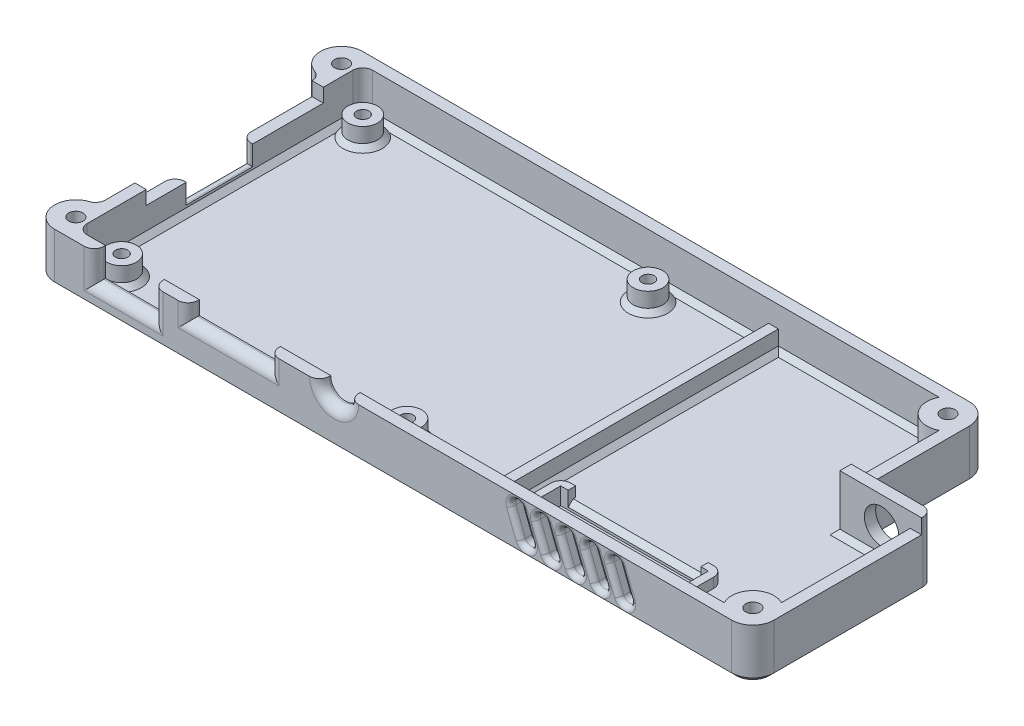
SolidWorks part; units mm, degrees
ref_plane "Front Plane" through (0, 0, 0) normal (0, 0, 1) x (1, 0, 0)
ref_plane "Top Plane" through (0, 0, 0) normal (0, 1, 0) x (1, 0, 0)
ref_plane "Right Plane" through (0, 0, 0) normal (1, 0, 0) x (0, 0, -1)
sketch "Sketch1" plane through (0, 0, 0) normal (0, 1, 0) x (1, 0, 0)
  line L0 (-71.5618, 3.106) -> (49.4382, 3.106) construction
  line L1 (-71.5618, 31.106) -> (49.4382, 31.106)
  line L2 (-71.5618, 31.106) -> (-71.5618, -24.894)
  line L3 (-71.5618, -24.894) -> (49.4382, -24.894)
  line L4 (49.4382, 31.106) -> (49.4382, -24.894)
  line L5 (-60.6618, -24.894) -> (-60.6618, -31.6828) construction
  line L6 (-68.0618, 27.606) -> (-10.0618, 27.606)
  line L7 (-68.0618, 27.606) -> (-68.0618, -21.394)
  line L8 (-68.0618, -21.394) -> (-10.0618, -21.394)
  line L9 (-10.0618, 27.606) -> (-10.0618, -21.394)
  line L10 (-39.5618, -24.894) -> (-39.5618, -31.6828) construction
  line L11 (-18.0618, -24.894) -> (-18.0618, -31.6828) construction
  line L12 (-65.4118, -26.5648) -> (-55.9118, -26.5648) construction
  line L13 (-48.0618, -26.5648) -> (-31.0618, -26.5648) construction
  line L14 (-22.0618, -26.5648) -> (-14.0618, -26.5648) construction
  line L15 (-72.5618, 9.606) -> (-72.5618, -3.394) construction
  line L16 (-71.5618, 3.106) -> (-72.5618, 3.106) construction
  dimension "D1" = 121
  dimension "D2" = 56
  dimension "D3" = 49
  dimension "D4" = 58
  dimension "D5" = 3.5
  dimension "D6" = 3.5
  dimension "D7" = 10.9
  dimension "D8" = 32
  dimension "D9" = 53.5
  dimension "D10" = 2
  dimension "D11" = 13
  dimension "D12" = 9.5
  dimension "D13" = 17
  dimension "D14" = 8
sketch "Sketch3" plane through (0, 0, 0) normal (0, 1, 0) x (1, 0, 0)
  line L0 (55.0382, -25.894) -> (64.7382, -25.894)
  line L1 (52.7382, 8.406) -> (67.0382, 8.406)
  line L2 (55.0382, 6.106) -> (64.7382, 6.106) construction
  line L3 (52.7382, -28.194) -> (67.0382, -28.194)
  line L4 (52.7382, 34.406) -> (-74.8618, 34.406)
  line L5 (-74.8618, 34.406) -> (-74.8618, -28.194)
  line L6 (-74.8618, -28.194) -> (52.7382, -28.194)
  line L7 (52.7382, 8.406) -> (52.7382, 34.406)
  line L8 (50.4382, 32.106) -> (-72.5618, 32.106)
  line L9 (50.4382, -25.894) -> (50.4382, 32.106)
  line L10 (-72.5618, -25.894) -> (50.4382, -25.894)
  line L11 (-72.5618, 32.106) -> (-72.5618, -25.894)
  line L12 (50.4382, 32.106) -> (-72.5618, 32.106)
  line L13 (50.4382, 6.106) -> (50.4382, 32.106)
  line L14 (-72.5618, -25.894) -> (50.4382, -25.894)
  line L15 (-72.5618, 32.106) -> (-72.5618, -25.894)
  line L16 (-11.0618, 3.106) -> (-11.0618, 34.406) construction
  line L17 (-71.5618, 3.106) -> (49.4382, 3.106) construction
  line L18 (67.0382, 8.406) -> (67.0382, -28.194)
  line L19 (64.7382, 6.106) -> (64.7382, -25.894)
  line L20 (-74.8618, 3.106) -> (52.7382, 3.106) construction
  line L21 (50.4382, 6.106) -> (64.7382, 6.106)
  line L22 (55.0382, -25.894) -> (50.4382, -25.894)
  line L23 (55.0382, 6.106) -> (55.0382, -25.894) construction
  line L24 (52.7382, 8.406) -> (52.7382, -28.194) construction
  line L25 (52.7382, -28.194) -> (52.7382, 34.406) construction
  line L26 (50.4382, -25.894) -> (50.4382, 32.106) construction
  dimension "D3" = 2.3
  dimension "D4" = 26
  dimension "D5" = 12
  dimension "D1" = 1
  dimension "D2" = 2.3
extrude "Boss-Extrude1" add sketch "Sketch3" along normal blind 10.3
sketch "Sketch5" plane through (0, 0, 0) normal (0, 1, 0) x (1, 0, 0)
  line L1 (-72.5618, 32.106) -> (50.4382, 32.106)
  line L2 (-72.5618, 32.106) -> (-72.5618, -25.894)
  line L3 (-72.5618, -25.894) -> (50.4382, -25.894)
  line L4 (50.4382, 32.106) -> (50.4382, 6.106)
  line L5 (50.4382, 6.106) -> (64.7382, 6.106)
  line L7 (50.4382, -25.894) -> (64.7382, -25.894)
  line L8 (64.7382, 6.106) -> (64.7382, -25.894)
extrude "Boss-Extrude2" add sketch "Sketch5" along normal blind 2
sketch "Sketch6" plane through (0, 2, 0) normal (0, 1, 0) x (1, 0, 0)
  circle A0 centre (-68.0618, 27.606) radius 3
  circle A1 centre (-68.0618, -21.394) radius 3
  circle A2 centre (-10.0618, -21.394) radius 3
  circle A3 centre (-10.0618, 27.606) radius 3
extrude "Boss-Extrude3" add sketch "Sketch6" along normal blind 4
hole_wizard "Ø2.5 (2.5) Diameter Hole1" positions "Sketch8" profile "Sketch9" hole size "Ø2.5" standard "ANSI Metric"
sketch "Sketch8" plane through (0, 6, 0) normal (0, 1, 0) x (1, 0, 0)
  point P0 (-68.0618, 27.606)
  point P3 (-10.0618, 27.606)
  point P6 (-10.0618, -21.394)
  point P9 (-68.0618, -21.394)
sketch "Sketch9" plane through (-68.0618, 6, -27.606) normal (1, 0, 0) x (0, 0, 1)
  line L0 (0, 0) -> (0, 8.7511)
  line L1 (0, 8.7511) -> (1.25, 8)
  line L2 (1.25, 8) -> (1.25, 0)
  line L5 (1.25, 0) -> (0, 0)
  line L10 (0, 8.7511) -> (-1.25, 8) construction
  line L11 (0, -6.35) -> (0, 107.95) construction
  dimension "Hole Dia." = 2.5
  dimension "Hole Depth" = 8
  dimension "Drill Angle" = 118
sketch "Sketch10" plane through (0, 2, 0) normal (0, 1, 0) x (1, 0, 0)
  line L0 (50.4382, 32.106) -> (-72.5618, 32.106) construction
  line L1 (9.9382, 32.106) -> (11.9382, 32.106)
  line L2 (9.9382, 32.106) -> (9.9382, -25.894)
  line L3 (9.9382, -25.894) -> (11.9382, -25.894)
  line L4 (11.9382, 32.106) -> (11.9382, -25.894)
  line L5 (-72.5618, -25.894) -> (64.7382, -25.894) construction
  line L6 (-10.0618, 27.606) -> (-10.0618, -21.394) construction
  dimension "D1" = 2
  dimension "D2" = 20
extrude "Boss-Extrude4" add sketch "Sketch10" along normal blind 4
sketch "Sketch11" plane through (0, 0, 28.194) normal (0, 0, 1) x (1, 0, 0)
  line L0 (-74.8618, 10.3) -> (-74.8618, 0) construction
  line L1 (-66.8618, 10.3) -> (-54.8618, 10.3)
  line L2 (-66.8618, 10.3) -> (-66.8618, 4.5)
  line L3 (-66.8618, 4.5) -> (-54.8618, 4.5)
  line L4 (-54.8618, 10.3) -> (-54.8618, 4.5)
  line L5 (-74.8618, 0) -> (67.0382, 0) construction
  line L6 (-60.8618, 10.3) -> (-60.6618, 0) construction
  line L7 (-65.4118, 0) -> (-55.9118, 0) construction
  line L9 (-47.778, 10.3) -> (-31.278, 10.3)
  line L10 (-47.778, 10.3) -> (-47.778, 7.5)
  line L11 (-47.778, 7.5) -> (-31.278, 7.5)
  line L12 (-31.278, 10.3) -> (-31.278, 7.5)
  line L13 (-68.0618, 0) -> (-10.0618, 0) construction
  line L14 (-39.5618, 0) -> (-39.528, 10.3) construction
  line L15 (-48.0618, 0) -> (-31.0618, 0) construction
  line L16 (-18.0618, 0) -> (-18.0618, 10.3) construction
  line L17 (-22.0618, 0) -> (-14.0618, 0) construction
  line L18 (-74.8618, 10.3) -> (67.0382, 10.3) construction
  circle A0 centre (-18.0618, 10.3) radius 3
  dimension "D5" = 6
  dimension "D1" = 4.5
  dimension "D2" = 12
  dimension "D3" = 7.5
  dimension "D4" = 16.5
  dimension "D6" = 8
extrude "Cut-Extrude1" cut sketch "Sketch11" against normal up to next
sketch "Sketch12" plane through (-74.8618, 0, 0) normal (-1, 0, 0) x (0, 0, 1)
  line L0 (-3.106, 0) -> (-3.106, 10.3) construction
  line L1 (-27.606, 0) -> (21.394, 0) construction
  line L2 (-34.406, 10.3) -> (28.194, 10.3) construction
  line L4 (-9.7329, 10.3) -> (3.7671, 10.3)
  line L5 (-9.7329, 10.3) -> (-9.7329, 3.5)
  line L6 (-9.7329, 3.5) -> (3.7671, 3.5)
  line L7 (3.7671, 10.3) -> (3.7671, 3.5)
  line L8 (-24.106, 10.3) -> (11.894, 10.3)
  line L9 (-24.106, 10.3) -> (-24.106, 7.5)
  line L10 (-24.106, 7.5) -> (11.894, 7.5)
  line L11 (11.894, 10.3) -> (11.894, 7.5)
  dimension "D1" = 13.5
  dimension "D2" = 3.5
  dimension "D3" = 7.5
  dimension "D4" = 36
extrude "Cut-Extrude2" cut sketch "Sketch12" against normal up to next contours L10 L11 L8 L9 | L7 L6 L5 L4
fillet "Fillet6" radius 2 1 edges at (50.4382, 6.15, -32.106)
fillet "Fillet8" radius 2 2 edges at (-72.5618, 6.15, 25.894) (-72.5618, 6.15, -32.106)
chamfer "Chamfer1" distance 1 angle 45 4 edges at (-68.0618, 2, 24.394) (-10.0618, 2, 24.394) (-10.0618, 2, -24.606) (-68.0618, 2, -24.606)
chamfer "Chamfer2" distance 1 angle 45 13 edges at (11.9382, 2, -3.106) (38.3382, 2, 25.894) (30.1882, 2, -32.106) (49.8524, 2, -31.5202) (50.4382, 2, -18.106) (-30.3118, 2, 25.894) (-71.976, 2, 25.3082) (-72.5618, 2, -3.106) (-71.976, 2, -31.5202) (9.9382, 2, -3.106) (-30.3118, 2, -32.106) (64.7382, 2, 9.894) (57.5882, 2, -6.106)
fillet "Fillet9" radius 2 9 edges at (-74.8618, 5.5, -9.7329) (-74.8618, 3.5, -2.9829) (-74.8618, 5.5, 3.7671) (-18.0618, 7.3, 28.194) (-31.278, 8.9, 28.194) (-47.778, 8.9, 28.194) (-39.528, 7.5, 28.194) (-54.8618, 7.4, 28.194) (-60.8618, 4.5, 28.194)
sketch "Sketch14" plane through (0, 10.3, 0) normal (0, 1, 0) x (1, 0, 0)
  line L1 (50.4382, 6.106) -> (67.0382, 6.106)
  line L2 (50.4382, 6.106) -> (50.4382, 8.406)
  line L3 (50.4382, 8.406) -> (67.0382, 8.406)
  line L4 (67.0382, 6.106) -> (67.0382, 8.406)
extrude "Boss-Extrude5" add sketch "Sketch14" along normal blind 3
sketch "Sketch13" plane through (0, 0, -8.406) normal (0, 0, -1) x (-1, 0, 0)
  circle A0 centre (-58.909, 7.7223) radius 3.5
extrude "Cut-Extrude3" cut sketch "Sketch13" against normal up to next
sketch "Sketch17" plane through (0, 0, 0) normal (0, 1, 0) x (1, 0, 0)
  line L0 (-74.8618, 34.406) -> (-74.8618, 24.106) construction
  line L1 (-74.8618, 34.406) -> (-74.8618, 25.806)
  line L2 (-74.8618, 25.806) -> (-74.659, 25.9406)
  line L3 (-74.8618, -19.594) -> (-74.8618, -28.194)
  line L4 (-74.8618, -28.194) -> (-74.659, -28.0594)
  arc A0 (-74.8618, -19.594) -> (-74.8618, -28.194) centre (-74.8618, -23.894) ccw
  arc A1 (-74.8618, 34.406) -> (-74.8618, 25.806) centre (-74.8618, 30.106) ccw
extrude "Boss-Extrude6" add sketch "Sketch17" along normal up to vertex (10.3 mm away) contours L1 A1 | L3 A0 region at (-76.6867, 0, -30.106) region at (-76.6867, 0, 23.894) up to point (-74.8618, 10.3, 28.194)
hole_wizard "Ø2.9 (2.9) Diameter Hole2" positions "Sketch19" profile "Sketch18" hole size "Ø2.9" standard "ANSI Metric" end condition up to next
sketch "Sketch19" plane through (0, 10.3, 0) normal (0, 1, 0) x (1, 0, 0)
  point P0 (-74.8618, 30.106)
sketch "Sketch18" plane through (-74.8618, 10.3, -30.106) normal (1, 0, 0) x (0, 0, 1)
  line L0 (0, 0) -> (0, 10.3)
  line L1 (0, 10.3) -> (1.45, 10.3)
  line L2 (1.45, 10.3) -> (1.45, 0)
  line L5 (1.45, 0) -> (0, 0)
  line L11 (0, -6.35) -> (0, 107.95) construction
  dimension "Thru Hole Dia." = 2.9
  dimension "Thru Hole Depth" = 10.3
hole_wizard "Ø2.9 (2.9) Diameter Hole1" positions "Sketch21" profile "Sketch20" hole size "Ø2.9" standard "ANSI Metric" end condition up to next
sketch "Sketch21" plane through (0, 10.3, 0) normal (0, 1, 0) x (1, 0, 0)
  point P0 (-74.8618, -23.894)
sketch "Sketch20" plane through (-74.8618, 10.3, 23.894) normal (1, 0, 0) x (0, 0, 1)
  line L0 (0, 0) -> (0, 10.3)
  line L1 (0, 10.3) -> (1.45, 10.3)
  line L2 (1.45, 10.3) -> (1.45, 0)
  line L5 (1.45, 0) -> (0, 0)
  line L11 (0, -6.35) -> (0, 107.95) construction
  dimension "Thru Hole Dia." = 2.9
  dimension "Thru Hole Depth" = 10.3
sketch "Sketch24" plane through (0, 2, 0) normal (0, 1, 0) x (1, 0, 0)
  circle A0 centre (62.7384, -23.8858) radius 4.3
  circle A1 centre (48.4185, 30.106) radius 4.3
extrude "Boss-Extrude7" add sketch "Sketch24" along normal up to surface (8.3 mm away) up to face at (-74.8618, 10.3, 25.344)
hole_wizard "Ø2.9 (2.9) Diameter Hole3" positions "Sketch26" profile "Sketch25" hole size "Ø2.9" standard "ANSI Metric" end condition up to next
sketch "Sketch26" plane through (0, 10.3, 0) normal (0, 1, 0) x (1, 0, 0)
  point P0 (62.7384, -23.8858)
sketch "Sketch25" plane through (62.7384, 10.3, 23.8858) normal (1, 0, 0) x (0, 0, 1)
  line L0 (0, 0) -> (0, 10.3)
  line L1 (0, 10.3) -> (1.45, 10.3)
  line L2 (1.45, 10.3) -> (1.45, 0)
  line L5 (1.45, 0) -> (0, 0)
  line L11 (0, -6.35) -> (0, 107.95) construction
  dimension "Thru Hole Dia." = 2.9
  dimension "Thru Hole Depth" = 10.3
hole_wizard "Ø2.9 (2.9) Diameter Hole4" positions "Sketch28" profile "Sketch27" hole size "Ø2.9" standard "ANSI Metric" end condition up to next
sketch "Sketch28" plane through (0, 10.3, 0) normal (0, 1, 0) x (1, 0, 0)
  point P0 (48.4185, 30.106)
sketch "Sketch27" plane through (48.4185, 10.3, -30.106) normal (1, 0, 0) x (0, 0, 1)
  line L0 (0, 0) -> (0, 10.3)
  line L1 (0, 10.3) -> (1.45, 10.3)
  line L2 (1.45, 10.3) -> (1.45, 0)
  line L5 (1.45, 0) -> (0, 0)
  line L11 (0, -6.35) -> (0, 107.95) construction
  dimension "Thru Hole Dia." = 2.9
  dimension "Thru Hole Depth" = 10.3
fillet "Fillet10" radius 4.3 1 edges at (52.7382, 5.15, -34.406)
fillet "Fillet16" radius 4.3 1 edges at (67.0382, 5.15, 28.194)
fillet "Fillet17" radius 2 2 edges at (52.7382, 5.15, -8.406) (67.0382, 6.65, -8.406)
fillet "Fillet18" radius 2 2 edges at (-74.8618, 5.15, 19.594) (-74.8618, 5.15, -25.806)
fillet "Fillet19" radius 2 1 edges at (-66.8618, 6.4, 28.194)
sketch "Sketch29" plane through (0, 2, 0) normal (0, 1, 0) x (1, 0, 0)
  line L1 (15.4382, -15.644) -> (45.5382, -15.644)
  line L2 (15.4382, -15.644) -> (15.4382, -25.894)
  line L3 (15.4382, -25.894) -> (45.5382, -25.894)
  line L4 (45.5382, -15.644) -> (45.5382, -25.894)
  line L5 (-72.5618, -11.894) -> (-72.5618, -23.894) construction
  line L6 (-13.0618, -28.194) -> (62.7382, -28.194) construction
  dimension "D1" = 30.1
  dimension "D2" = 10.25
  dimension "D3" = 88
  dimension "D4" = 2.3
extrude "Cut-Extrude4" cut sketch "Sketch29" against normal blind 1.5 and the other way up to next
sketch "Sketch30" plane through (0, 2, 0) normal (0, 1, 0) x (1, 0, 0)
  line L4 (13.9382, -25.9084) -> (15.4382, -25.894)
  line L5 (15.4382, -25.894) -> (15.4382, -15.644)
  line L6 (15.4382, -15.644) -> (16.9593, -15.644)
  line L7 (45.4382, -15.644) -> (45.4382, -25.894)
  line L8 (13.9382, -14.144) -> (13.9382, -27.394)
  line L9 (13.9382, -27.394) -> (47.0382, -27.394)
  line L10 (47.0382, -27.394) -> (47.0382, -14.144)
  line L11 (47.0382, -14.144) -> (13.9382, -14.144)
  line L12 (13.9382, -14.144) -> (13.9382, -25.9084)
  line L13 (16.9593, -14.144) -> (16.9593, -15.644)
  line L14 (47.0382, -25.894) -> (47.0382, -14.144)
  line L15 (47.0382, -14.144) -> (43.9171, -14.144)
  line L16 (45.4382, -25.894) -> (47.0382, -25.894)
  line L17 (30.4382, -16.444) -> (30.4382, -22.6133) construction
  line L18 (43.9171, -14.144) -> (43.9171, -15.644)
  line L19 (16.9593, -14.144) -> (13.9382, -14.144)
  line L20 (43.9171, -15.644) -> (45.4382, -15.644)
  dimension "D1" = 1.5
extrude "Boss-Extrude8" add sketch "Sketch30" along normal blind 2
chamfer "Chamfer3" distance 1 angle 45 1 edges at (30.4382, 2, 15.644)
fillet "Fillet20" radius 2 2 edges at (13.9382, 3, 14.144) (47.0382, 3, 14.144)
sketch "Sketch31" plane through (0, 0, 28.194) normal (0, 0, 1) x (1, 0, 0)
  line L0 (19.0803, 8.1204) -> (20.9966, 3.179) construction
  line L2 (20.2457, 8.5724) -> (22.1621, 3.6309)
  line L3 (17.9149, 7.6684) -> (19.8312, 2.727)
  line L4 (24.0803, 8.1204) -> (25.9966, 3.179) construction
  line L5 (25.2457, 8.5724) -> (27.1621, 3.6309)
  line L6 (22.9149, 7.6684) -> (24.8312, 2.727)
  line L7 (29.0803, 8.1204) -> (30.9966, 3.179) construction
  line L8 (30.2457, 8.5724) -> (32.1621, 3.6309)
  line L9 (27.9149, 7.6684) -> (29.8312, 2.727)
  line L10 (34.0803, 8.1204) -> (35.9966, 3.179) construction
  line L11 (35.2457, 8.5724) -> (37.1621, 3.6309)
  line L12 (32.9149, 7.6684) -> (34.8312, 2.727)
  line L13 (39.0803, 8.1204) -> (40.9966, 3.179) construction
  line L14 (40.2457, 8.5724) -> (42.1621, 3.6309)
  line L15 (37.9149, 7.6684) -> (39.8312, 2.727)
  arc A0 (20.2457, 8.5724) -> (17.9149, 7.6684) centre (19.0803, 8.1204) ccw
  arc A1 (19.8312, 2.727) -> (22.1621, 3.6309) centre (20.9966, 3.179) ccw
  arc A2 (25.2457, 8.5724) -> (22.9149, 7.6684) centre (24.0803, 8.1204) ccw
  arc A3 (24.8312, 2.727) -> (27.1621, 3.6309) centre (25.9966, 3.179) ccw
  arc A4 (30.2457, 8.5724) -> (27.9149, 7.6684) centre (29.0803, 8.1204) ccw
  arc A5 (29.8312, 2.727) -> (32.1621, 3.6309) centre (30.9966, 3.179) ccw
  arc A6 (35.2457, 8.5724) -> (32.9149, 7.6684) centre (34.0803, 8.1204) ccw
  arc A7 (34.8312, 2.727) -> (37.1621, 3.6309) centre (35.9966, 3.179) ccw
  arc A8 (40.2457, 8.5724) -> (37.9149, 7.6684) centre (39.0803, 8.1204) ccw
  arc A9 (39.8312, 2.727) -> (42.1621, 3.6309) centre (40.9966, 3.179) ccw
  point P4 (20.0385, 5.6497)
  point P13 (25.0385, 5.6497)
  point P20 (30.0385, 5.6497)
  point P27 (35.0385, 5.6497)
  point P34 (40.0385, 5.6497)
  dimension "D1" = 5
extrude "Cut-Extrude5" cut sketch "Sketch31" against normal up to next
chamfer "Chamfer5" distance 1 angle 45 14 edges at (-79.1058, 0, 24.5855) (-6.0618, 0, 28.194) (-75.2385, 0, 19.0883) (65.7788, 0, 26.9346) (-74.8618, 0, -3.106) (67.0382, 0, 8.744) (-75.2385, 0, -25.3002) (66.4524, 0, -7.8202) (-79.1058, 0, -30.7975) (59.8882, 0, -8.406) (-13.2118, 0, -34.406) (53.324, 0, -8.9918) (51.4788, 0, -33.1466) (52.7382, 0, -20.256)
fillet "Fillet21" radius 1 20 edges at (38.6284, 9.2858, 28.194) (41.2039, 6.1016, 28.194) (41.4486, 2.0135, 28.194) (33.6284, 9.2858, 28.194) (36.2039, 6.1016, 28.194) (36.4486, 2.0135, 28.194) (28.6284, 9.2858, 28.194) (31.2039, 6.1016, 28.194) (31.4486, 2.0135, 28.194) (23.6284, 9.2858, 28.194) (26.2039, 6.1016, 28.194) (26.4486, 2.0135, 28.194) (18.6284, 9.2858, 28.194) (21.2039, 6.1016, 28.194) (21.4486, 2.0135, 28.194) (38.873, 5.1977, 28.194) (33.873, 5.1977, 28.194) (28.873, 5.1977, 28.194) (23.873, 5.1977, 28.194) (18.873, 5.1977, 28.194)
